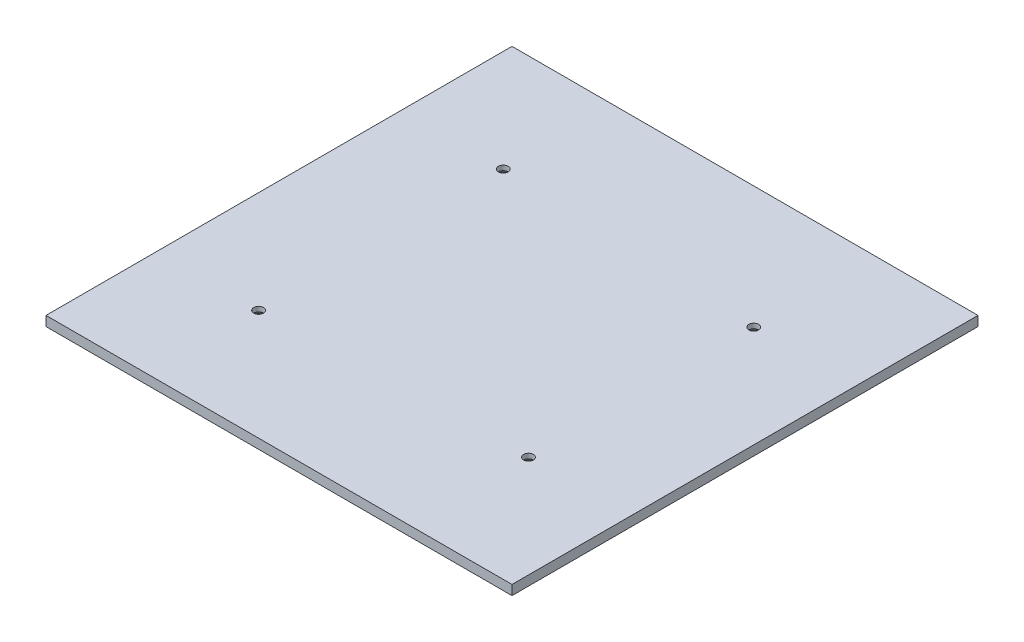
SolidWorks part; units mm, degrees
material "6061-T4 (SS)"
ref_plane "Front Plane" through (0, 0, 0) normal (0, 0, 1) x (1, 0, 0)
ref_plane "Top Plane" through (0, 0, 0) normal (0, 1, 0) x (1, 0, 0)
ref_plane "Right Plane" through (0, 0, 0) normal (1, 0, 0) x (0, 0, -1)
sketch "Sketch1" plane through (0, 0, 0) normal (0, 1, 0) x (1, 0, 0)
  line L0 (76.2, 0) -> (76.2, 152.4) construction
  line L1 (0, 0) -> (152.4, 0)
  line L2 (0, 0) -> (0, 152.4)
  line L3 (0, 152.4) -> (152.4, 152.4)
  line L4 (152.4, 0) -> (152.4, 152.4)
  point P7 (76.2, 76.2)
  dimension "D1" = 152.4
  dimension "D2" = 152.4
extrude "Boss-Extrude1" add sketch "Sketch1" along normal blind 3.175
sketch "Sketch3" plane through (0, 3.175, 0) normal (0, 1, 0) x (1, 0, 0)
  line L0 (76.2, 152.4) -> (76.2, 0) construction
  line L1 (152.4, 152.4) -> (0, 152.4) construction
  line L2 (0, 0) -> (152.4, 0) construction
  line L3 (76.2, 76.2) -> (152.4, 76.2) construction
  line L4 (152.4, 0) -> (152.4, 152.4) construction
ref_plane "Plane1" through (76.2, 0, 0) normal (1, 0, 0) x (0, 0, -1)
sketch "Sketch4" plane through (76.2, 0, 0) normal (1, 0, 0) x (0, 0, -1)
  line L0 (76.2, 3.175) -> (76.2, 119.4805) construction
sketch "Sketch5" plane through (0, 3.175, 0) normal (0, 1, 0) x (1, 0, 0)
  circle A0 centre (119.0625, 38.735) radius 1.6
  circle A1 centre (119.0625, 112.395) radius 1.6
  circle A2 centre (33.3375, 116.205) radius 1.6
  circle A3 centre (33.3375, 36.195) radius 1.6
  circle A4 centre (33.3375, 36.195) radius 1.6 construction
  circle A5 centre (119.0625, 38.735) radius 1.6 construction
  circle A6 centre (119.0625, 112.395) radius 1.6 construction
  circle A7 centre (33.3375, 116.205) radius 1.6 construction
hole_wizard "Hole1" positions "Sketch8" profile "Sketch7" legacy
sketch "Sketch8" plane through (0, 0, 0) normal (0, -1, 0) x (-1, 0, 0)
  point P0 (-119.0625, 38.735)
  point P2 (-33.3375, 36.195)
  point P4 (-33.3375, 116.205)
  point P6 (-119.0625, 112.395)
sketch "Sketch7" plane through (119.0625, 0, -38.735) normal (1, 0, 0) x (0, 0, -1)
  line L0 (0, 0) -> (0, 99.9872)
  line L1 (0, 99.9872) -> (1.6, 99.9872)
  line L2 (1.6, 99.9872) -> (1.6, 1.6)
  line L3 (1.6, 1.6) -> (3.2, 0)
  line L4 (3.2, 0) -> (0, 0)
  line L5 (0, -6.4453) -> (0, 115.525) construction
  line L6 (-1.6, 1.6) -> (-3.2, 0) construction
  dimension "Diameter" = 3.2
  dimension "Depth" = 100
  dimension "C-Sink Angle" = 90
  dimension "C-Sink Diameter" = 6.4
